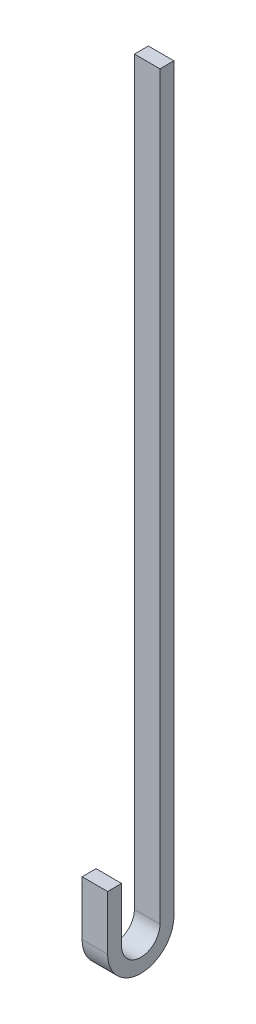
SolidWorks part; units mm, degrees
ref_plane "Front" through (0, 0, 0) normal (0, 0, 1) x (1, 0, 0)
ref_plane "Top" through (0, 0, 0) normal (0, 1, 0) x (1, 0, 0)
ref_plane "Right" through (0, 0, 0) normal (1, 0, 0) x (0, 0, -1)
sketch "Sketch1" plane through (0, 0, 0) normal (1, 0, 0) x (0, 0, -1)
  line L0 (0, 0) -> (0, -58.4425)
  line L1 (71.12, -58.4425) -> (71.12, 736.6)
  line L2 (14.986, 0) -> (14.986, -58.4425)
  line L3 (56.134, -58.4425) -> (56.134, 736.6)
  line L4 (0, 0) -> (14.986, 0)
  line L5 (56.134, 736.6) -> (71.12, 736.6)
  line L7 (2.54, 736.6) -> (73.025, 736.6) construction
  arc A0 (0, -58.4425) -> (71.12, -58.4425) centre (35.56, -58.4425) ccw
  arc A1 (14.986, -58.4425) -> (56.134, -58.4425) centre (35.56, -58.4425) ccw
  point P11 (71.12, -158.4138)
  point P12 (56.134, 410.1125)
  point P13 (56.134, 535.2165)
  dimension "D1" = 965.2
  dimension "D2" = 71.12
  dimension "D4" = 41.148
  dimension "D3" = 14.986
extrude "Boss-Extrude1" add sketch "Sketch1" along normal blind 27.432
